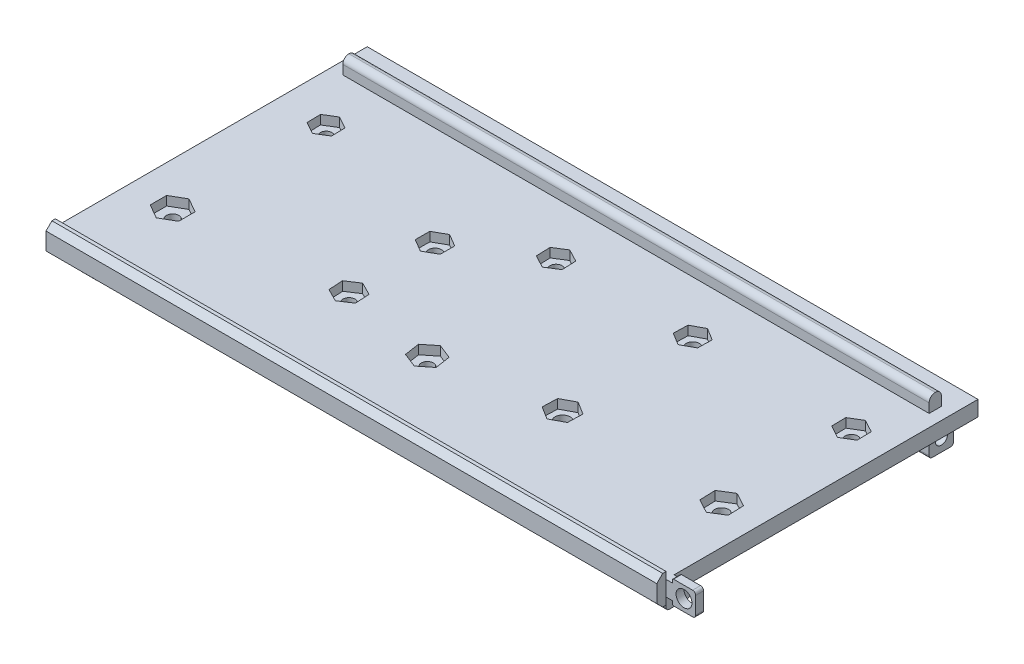
SolidWorks part; units mm, degrees
ref_plane "Alzado" through (0, 0, 0) normal (0, 0, 1) x (1, 0, 0)
ref_plane "Planta" through (0, 0, 0) normal (0, 1, 0) x (1, 0, 0)
ref_plane "Vista lateral" through (0, 0, 0) normal (1, 0, 0) x (0, 0, -1)
sketch "Croquis3" plane through (0, 0, 0) normal (0, 1, 0) x (1, 0, 0)
  line L1 (-116.001, 50) -> (83.999, 50)
  line L2 (-116.001, 50) -> (-116.001, -50)
  line L3 (-116.001, -50) -> (83.999, -50)
  line L4 (83.999, 50) -> (83.999, -50)
  circle A0 centre (19.4896, 21.1007) radius 2.45
  circle A1 centre (71.658, 20.902) radius 2.45
  circle A2 centre (71.3776, -21.3107) radius 2.45
  circle A3 centre (19.1425, -21.1883) radius 2.4502
  dimension "D4" = 4.9
  dimension "D5" = 4.9
  dimension "D6" = 4.9
  dimension "D1" = 100
  dimension "D2" = 50
  dimension "D3" = 200
extrude "Saliente-Extruir1" add sketch "Croquis3" along normal blind 5
sketch "Croquis23" plane through (0, 0, 0) normal (0, 1, 0) x (1, 0, 0)
  line L0 (-116.001, 50) -> (-116.001, -50) construction
  line L1 (-116.001, 23.3955) -> (-13.501, 23.3955) construction
  line L2 (-116.001, 23.3955) -> (-116.001, -30.6045) construction
  line L3 (-116.001, -30.6045) -> (-13.501, -30.6045) construction
  line L4 (-13.501, 23.3955) -> (-13.501, -30.6045) construction
  line L5 (83.999, 50) -> (-116.001, 50) construction
  dimension "D1" = 54
  dimension "D2" = 102.5
  dimension "D3" = 26.6045
sketch "Croquis24" plane through (0, 0, 0) normal (0, 1, 0) x (1, 0, 0)
  circle A0 centre (-25.0227, 20.8531) radius 1.9594
  circle A1 centre (-18.4981, -27.8259) radius 1.9784
  circle A2 centre (-49.4418, -22.529) radius 1.963
  circle A3 centre (-49.3008, 5.4861) radius 2.1255
  circle A4 centre (-100.4804, 20.9921) radius 1.8726
  circle A5 centre (-102.0157, -27.7009) radius 2.0276
sketch "Croquis4" plane through (0, 5, 0) normal (0, 1, 0) x (1, 0, 0)
  circle A0 centre (-25.0227, 20.8531) radius 1.9594
  circle A1 centre (-49.3008, 5.4861) radius 2.1255
  circle A2 centre (-49.4418, -22.529) radius 1.963
  circle A3 centre (-18.4981, -27.8259) radius 1.9784
  circle A4 centre (-102.0157, -27.7009) radius 2.0276
  circle A5 centre (-100.4804, 20.9921) radius 1.8726
  circle A6 centre (-100.4804, 20.9921) radius 3.8726
  circle A7 centre (-102.0157, -27.7009) radius 4.0276
  circle A8 centre (-49.4418, -22.529) radius 3.963
  circle A9 centre (-18.4981, -27.8259) radius 3.9784
  circle A10 centre (-25.0227, 20.8531) radius 3.9594
  circle A11 centre (-49.3008, 5.4861) radius 4.1255
  circle A95 centre (19.4896, 21.1007) radius 2.1242
  circle A96 centre (71.658, 20.902) radius 2.0314
  circle A97 centre (71.3776, -21.3107) radius 2.2649
  circle A98 centre (19.1425, -21.1883) radius 2.4502
  circle A104 centre (19.1425, -21.1883) radius 4.4502
  circle A105 centre (19.4896, 21.1007) radius 4.1242
  circle A106 centre (71.658, 20.902) radius 4.0314
  circle A107 centre (71.3776, -21.3107) radius 4.2649
  dimension "D1" = 2
  dimension "D2" = 2
extrude "Saliente-Extruir2" add sketch "Croquis4" against normal blind 9
sketch "Croquis7" plane through (83.999, 0, 0) normal (1, 0, 0) x (0, 0, -1)
  line L0 (-50, 0) -> (50, 0) construction
  line L1 (-50, -7.5) -> (-70, -7.5) construction
  line L2 (-50, -7.5) -> (-50, 12.5) construction
  line L3 (-50, 12.5) -> (-70, 12.5) construction
  line L4 (-70, -7.5) -> (-70, 12.5) construction
  line L5 (-50, 5) -> (-50, 0) construction
  dimension "D1" = 7.5
  dimension "D2" = 20
  dimension "D3" = 20
sketch "Croquis8" plane through (83.999, 0, 0) normal (1, 0, 0) x (0, 0, -1)
  line L0 (-50, 5) -> (-52.133, 5)
  line L1 (-52.133, 5) -> (-52.133, 7.2643)
  line L2 (-52.133, 7.2643) -> (-53.25, 7.2643)
  line L3 (-53.25, 7.2643) -> (-55.1863, 5.328)
  line L4 (-55.1863, 5.328) -> (-55.1863, -0.328)
  line L5 (-55.1863, 2.5) -> (-37.6856, 2.5) construction
  line L6 (-53.25, -2.2643) -> (-55.1863, -0.328)
  line L7 (-52.133, -2.2643) -> (-53.25, -2.2643)
  line L8 (-52.133, 0) -> (-52.133, -2.2643)
  line L9 (-50, 0) -> (-52.133, 0)
  line L10 (-50, 5) -> (-50, 0)
extrude "Saliente-Extruir3" add sketch "Croquis8" against normal blind 200
sketch "Croquis9" plane through (0, 0, 0) normal (0, -1, 0) x (1, 0, 0)
  line L0 (-116.001, 52.133) -> (83.999, 52.133) construction
  line L1 (-112.001, 48.133) -> (-107.001, 48.133)
  line L2 (-112.001, 48.133) -> (-112.001, 40.133)
  line L3 (-112.001, 40.133) -> (-107.001, 40.133)
  line L4 (-107.001, 48.133) -> (-107.001, 40.133)
  line L5 (74.999, 40.133) -> (79.999, 40.133)
  line L6 (79.999, 48.133) -> (79.999, 40.133)
  line L7 (74.999, 48.133) -> (79.999, 48.133)
  line L8 (74.999, 48.133) -> (74.999, 40.133)
  line L9 (74.999, -46) -> (79.999, -46)
  line L10 (79.999, -38) -> (79.999, -46)
  line L11 (74.999, -38) -> (79.999, -38)
  line L12 (74.999, -38) -> (74.999, -46)
  line L13 (-112.001, -46) -> (-107.001, -46)
  line L14 (-107.001, -38) -> (-107.001, -46)
  line L15 (-112.001, -38) -> (-107.001, -38)
  line L16 (-112.001, -38) -> (-112.001, -46)
  line L17 (-116.001, -50) -> (-116.001, 52.133) construction
  line L18 (83.999, 52.133) -> (83.999, -50) construction
  line L19 (83.999, -50) -> (-116.001, -50) construction
  dimension "D1" = 8
  dimension "D2" = 5
  dimension "D3" = 4
  dimension "D6" = 4
  dimension "D7" = 4
  dimension "D8" = 4
  dimension "D4" = 2
  dimension "D5" = 2
extrude "Saliente-Extruir4" add sketch "Croquis9" along normal blind 8
fillet "Redondeo1" radius 1 8 edges at (-109.501, -8, 40.133) (-109.501, -8, 48.133) (-109.501, -8, -38) (-109.501, -8, -46) (77.499, -8, -38) (77.499, -8, -46) (77.499, -8, 40.133) (77.499, -8, 48.133)
sketch "Croquis11" plane through (0, 0, 0) normal (0, -1, 0) x (1, 0, 0)
  line L0 (83.999, -50) -> (-116.001, -50) construction
  line L1 (-57.4359, -46) -> (-49.4359, -46)
  line L2 (-57.4359, -46) -> (-57.4359, -40)
  line L3 (-57.4359, -40) -> (-49.4359, -40)
  line L4 (-49.4359, -46) -> (-49.4359, -40)
  line L5 (42.5641, -40) -> (50.5641, -40)
  line L6 (42.5641, -46) -> (50.5641, -46)
  line L7 (42.5641, -46) -> (42.5641, -40)
  line L8 (50.5641, -46) -> (50.5641, -40)
  dimension "D1" = 4
  dimension "D2" = 6
  dimension "D3" = 8
  dimension "D4" = 2
extrude "Saliente-Extruir5" add sketch "Croquis11" along normal blind 8
fillet "Redondeo3" radius 2 4 edges at (-57.4359, -8, -43) (-49.4359, -8, -43) (42.5641, -8, -43) (50.5641, -8, -43)
sketch "Croquis12" plane through (0, 5, 0) normal (0, 1, 0) x (1, 0, 0)
  line L0 (-112.001, 38) -> (-112.001, 46) construction
  line L1 (-112.001, 42) -> (79.999, 42)
  line L2 (-112.001, 42) -> (-112.001, 38)
  line L3 (-112.001, 38) -> (79.999, 38)
  line L4 (79.999, 42) -> (79.999, 38)
extrude "Saliente-Extruir6" add sketch "Croquis12" along normal blind 5
fillet "Redondeo4" radius 2 2 edges at (-16.001, 10, -38) (-16.001, 10, -42)
sketch "Croquis13" plane through (-112.001, 0, 0) normal (-1, 0, 0) x (0, 0, 1)
  line L0 (-42, 0) -> (-42, -8) construction
  line L1 (-38, 0) -> (-46, 0) construction
  line L2 (-39, -8) -> (-45, -8) construction
  line L3 (44.133, 0) -> (44.133, -8) construction
  line L4 (48.133, 0) -> (40.133, 0) construction
  line L5 (47.133, -8) -> (41.133, -8) construction
  circle A0 centre (-42, -4) radius 2
  circle A1 centre (44.133, -4) radius 2
extrude "Cortar-Extruir3" cut sketch "Croquis13" against normal blind 6
sketch "Croquis14" plane through (79.999, 0, 0) normal (1, 0, 0) x (0, 0, -1)
  line L0 (-44.133, 0) -> (-44.133, -8) construction
  line L1 (-48.133, 0) -> (-40.133, 0) construction
  line L2 (-41.133, -8) -> (-47.133, -8) construction
  line L3 (42, 0) -> (42, -8) construction
  line L4 (38, 0) -> (46, 0) construction
  line L5 (45, -8) -> (39, -8) construction
  circle A0 centre (-44.133, -4) radius 2
  circle A1 centre (42, -4) radius 2
extrude "Cortar-Extruir4" cut sketch "Croquis14" against normal blind 6
sketch "Croquis15" plane through (0, 0, -46) normal (0, 0, -1) x (-1, 0, 0)
  line L0 (-46.5641, 0) -> (-46.5641, -8) construction
  line L1 (-42.5641, 0) -> (-50.5641, 0) construction
  line L2 (-44.5641, -8) -> (-48.5641, -8) construction
  line L3 (53.4359, 0) -> (53.4359, -8) construction
  line L4 (57.4359, 0) -> (49.4359, 0) construction
  line L5 (55.4359, -8) -> (51.4359, -8) construction
  circle A0 centre (-46.5641, -4) radius 2
  circle A1 centre (53.4359, -4) radius 2
extrude "Cortar-Extruir5" cut sketch "Croquis15" against normal blind 6
sketch "Croquis16" plane through (-107.001, 0, 0) normal (1, 0, 0) x (0, 0, -1)
  line L1 (39.158, -5.5894) -> (41.9555, -7.256)
  line L2 (41.9555, -7.256) -> (44.7975, -5.6665)
  line L3 (44.7975, -5.6665) -> (44.842, -2.4106)
  line L4 (44.842, -2.4106) -> (42.0445, -0.744)
  line L5 (42.0445, -0.744) -> (39.2025, -2.3335)
  line L6 (39.2025, -2.3335) -> (39.158, -5.5894)
  line L7 (-46.8652, -5.7714) -> (-43.965, -7.2519)
  line L8 (-43.965, -7.2519) -> (-41.2327, -5.4805)
  line L9 (-41.2327, -5.4805) -> (-41.4007, -2.2286)
  line L10 (-41.4007, -2.2286) -> (-44.3009, -0.7481)
  line L11 (-44.3009, -0.7481) -> (-47.0332, -2.5195)
  line L12 (-47.0332, -2.5195) -> (-46.8652, -5.7714)
  circle A0 centre (42, -4) radius 2.82 construction
  circle A1 centre (-44.133, -4) radius 2.82 construction
  dimension "D1" = 5.64
  dimension "D2" = 5.64
extrude "Cortar-Extruir6" cut sketch "Croquis16" against normal blind 2.6
pattern_linear "MatrizL1" count 2 spacing 184.6 along (1, 0, 0) of "Cortar-Extruir6"
sketch "Croquis17" plane through (0, 0, -40) normal (0, 0, 1) x (1, 0, 0)
  line L1 (49.376, -2.358) -> (46.5481, -0.7438)
  line L2 (46.5481, -0.7438) -> (43.7361, -2.3857)
  line L3 (43.7361, -2.3857) -> (43.7521, -5.642)
  line L4 (43.7521, -5.642) -> (46.5801, -7.2562)
  line L5 (46.5801, -7.2562) -> (49.392, -5.6143)
  line L6 (49.392, -5.6143) -> (49.376, -2.358)
  circle A0 centre (46.5641, -4) radius 2.82 construction
  dimension "D1" = 5.64
extrude "Cortar-Extruir7" cut sketch "Croquis17" against normal blind 2.6
pattern_linear "MatrizL2" count 2 spacing 100 along (-1, 0, 0) of "Cortar-Extruir7"
sketch "Croquis19" plane through (0, 0, 52.133) normal (0, 0, -1) x (-1, 0, 0)
  line L0 (-83.999, 0) -> (-83.999, 5) construction
  line L1 (-83.999, 2.5) -> (-95.7294, 2.5) construction
  line L2 (-83.999, 5) -> (-86.0596, 5)
  line L3 (-86.4596, -1.287) -> (-92.6688, -1.287)
  line L4 (-86.0596, -0.887) -> (-86.0596, 0)
  line L5 (-86.4596, 6.287) -> (-92.6688, 6.287)
  line L6 (-93.6688, -0.287) -> (-93.6688, 5.287)
  line L7 (-86.0596, -1.287) -> (-93.6688, 6.287) construction
  line L8 (-86.0596, 6.287) -> (-93.6688, -1.287) construction
  line L9 (-83.999, 0) -> (-86.0596, 0)
  line L10 (-86.0596, 5) -> (-86.0596, 5.887)
  line L11 (-83.999, 5) -> (-83.999, 0)
  circle A0 centre (-89.8642, 2.5) radius 2.6
  arc A1 (-92.6688, -1.287) -> (-93.6688, -0.287) centre (-92.6688, -0.287) cw
  arc A2 (-92.6688, 6.287) -> (-93.6688, 5.287) centre (-92.6688, 5.287) ccw
  arc A3 (-86.0596, 5.887) -> (-86.4596, 6.287) centre (-86.4596, 5.887) ccw
  arc A4 (-86.4596, -1.287) -> (-86.0596, -0.887) centre (-86.4596, -0.887) ccw
  dimension "D1" = 5.2
  dimension "D2" = 1
  dimension "D3" = 0.4
extrude "Saliente-Extruir7" add sketch "Croquis19" along normal blind 2.6
sketch "Croquis25" plane through (0, 0, 0) normal (0, 1, 0) x (1, 0, 0)
  circle A0 centre (-100.4804, 20.9921) radius 1.8726
  circle A1 centre (-49.3008, 5.4861) radius 2.1255
  circle A2 centre (-25.0227, 20.8531) radius 1.9594
  circle A3 centre (-18.4981, -27.8259) radius 1.9784
  circle A4 centre (-49.4418, -22.529) radius 1.963
  circle A5 centre (-102.0157, -27.7009) radius 2.0276
extrude "Cortar-Extruir8" cut sketch "Croquis25" along normal blind 10
sketch "Croquis26" plane through (0, 0, 0) normal (0, 1, 0) x (1, 0, 0)
  line L1 (-96.6079, 23.3462) -> (-100.5829, 25.5229)
  line L2 (-100.5829, 25.5229) -> (-104.4555, 23.1688)
  line L3 (-104.4555, 23.1688) -> (-104.353, 18.638)
  line L4 (-104.353, 18.638) -> (-100.378, 16.4613)
  line L5 (-100.378, 16.4613) -> (-96.5054, 18.8154)
  line L6 (-96.5054, 18.8154) -> (-96.6079, 23.3462)
  line L7 (-102.0157, -33.0677) -> (-97.368, -30.3843)
  line L8 (-97.368, -30.3843) -> (-97.368, -25.0176)
  line L9 (-97.368, -25.0176) -> (-102.0157, -22.3342)
  line L10 (-102.0157, -22.3342) -> (-106.6635, -25.0176)
  line L11 (-106.6635, -25.0176) -> (-106.6635, -30.3843)
  line L12 (-106.6635, -30.3843) -> (-102.0157, -33.0677)
  line L13 (-45.1753, 7.8278) -> (-49.266, 10.2298)
  line L14 (-49.266, 10.2298) -> (-53.3915, 7.8881)
  line L15 (-53.3915, 7.8881) -> (-53.4263, 3.1444)
  line L16 (-53.4263, 3.1444) -> (-49.3355, 0.7425)
  line L17 (-49.3355, 0.7425) -> (-45.21, 3.0842)
  line L18 (-45.21, 3.0842) -> (-45.1753, 7.8278)
  line L19 (-45.4788, -19.9227) -> (-49.7174, -17.7938)
  line L20 (-49.7174, -17.7938) -> (-53.6804, -20.4001)
  line L21 (-53.6804, -20.4001) -> (-53.4048, -25.1353)
  line L22 (-53.4048, -25.1353) -> (-49.1662, -27.2642)
  line L23 (-49.1662, -27.2642) -> (-45.2032, -24.6579)
  line L24 (-45.2032, -24.6579) -> (-45.4788, -19.9227)
  line L25 (-14.5198, -24.6579) -> (-19.2525, -22.7965)
  line L26 (-19.2525, -22.7965) -> (-23.2309, -25.9646)
  line L27 (-23.2309, -25.9646) -> (-22.4765, -30.9939)
  line L28 (-22.4765, -30.9939) -> (-17.7437, -32.8553)
  line L29 (-17.7437, -32.8553) -> (-13.7653, -29.6873)
  line L30 (-13.7653, -29.6873) -> (-14.5198, -24.6579)
  line L31 (-21.0633, 23.3462) -> (-25.2021, 25.5286)
  line L32 (-25.2021, 25.5286) -> (-29.1615, 23.0356)
  line L33 (-29.1615, 23.0356) -> (-28.9821, 18.3601)
  line L34 (-28.9821, 18.3601) -> (-24.8433, 16.1776)
  line L35 (-24.8433, 16.1776) -> (-20.8839, 18.6707)
  line L36 (-20.8839, 18.6707) -> (-21.0633, 23.3462)
  line L37 (23.6138, 23.3462) -> (19.607, 25.7951)
  line L38 (19.607, 25.7951) -> (15.4828, 23.5495)
  line L39 (15.4828, 23.5495) -> (15.3655, 18.8551)
  line L40 (15.3655, 18.8551) -> (19.3723, 16.4063)
  line L41 (19.3723, 16.4063) -> (23.4964, 18.6518)
  line L42 (23.4964, 18.6518) -> (23.6138, 23.3462)
  line L43 (75.6894, 23.3462) -> (71.5569, 25.6154)
  line L44 (71.5569, 25.6154) -> (67.5255, 23.1711)
  line L45 (67.5255, 23.1711) -> (67.6266, 18.4577)
  line L46 (67.6266, 18.4577) -> (71.7591, 16.1886)
  line L47 (71.7591, 16.1886) -> (75.7905, 18.6328)
  line L48 (75.7905, 18.6328) -> (75.6894, 23.3462)
  line L49 (75.7905, -18.566) -> (71.207, -16.1167)
  line L50 (71.207, -16.1167) -> (66.7941, -18.8614)
  line L51 (66.7941, -18.8614) -> (66.9647, -24.0554)
  line L52 (66.9647, -24.0554) -> (71.5481, -26.5048)
  line L53 (71.5481, -26.5048) -> (75.961, -23.7601)
  line L54 (75.961, -23.7601) -> (75.7905, -18.566)
  line L55 (23.4964, -18.8614) -> (19.3043, -16.2542)
  line L56 (19.3043, -16.2542) -> (14.9503, -18.5812)
  line L57 (14.9503, -18.5812) -> (14.7886, -23.5153)
  line L58 (14.7886, -23.5153) -> (18.9807, -26.1224)
  line L59 (18.9807, -26.1224) -> (23.3347, -23.7955)
  line L60 (23.3347, -23.7955) -> (23.4964, -18.8614)
  circle A0 centre (-100.4804, 20.9921) radius 3.9248 construction
  circle A1 centre (-102.0157, -27.7009) radius 4.6477 construction
  circle A2 centre (-49.3008, 5.4861) radius 4.1082 construction
  circle A3 centre (-49.4418, -22.529) radius 4.1077 construction
  circle A4 centre (-18.4981, -27.8259) radius 4.4043 construction
  circle A5 centre (-25.0227, 20.8531) radius 4.0521 construction
  circle A6 centre (19.4896, 21.1007) radius 4.0668 construction
  circle A7 centre (71.658, 20.902) radius 4.0829 construction
  circle A8 centre (71.3776, -21.3107) radius 4.5006 construction
  circle A9 centre (19.1425, -21.1883) radius 4.2753 construction
extrude "Cortar-Extruir9" cut sketch "Croquis26" along normal blind 14 from offset 2
